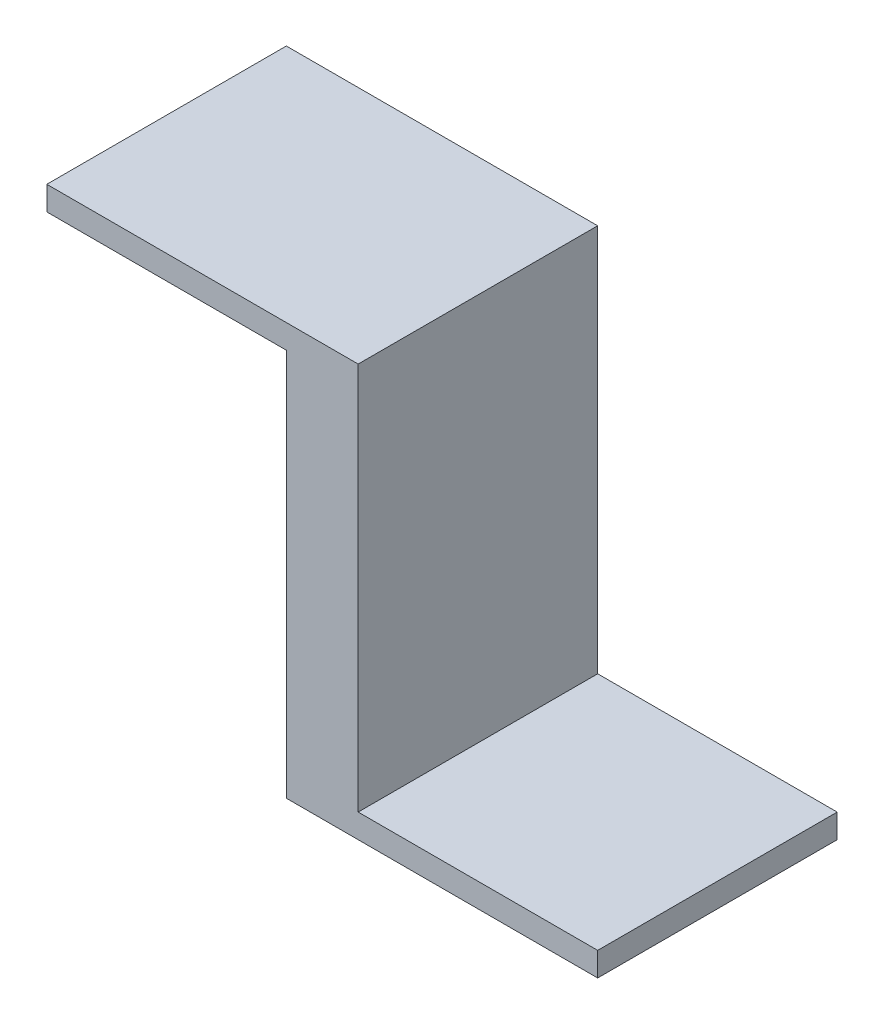
SolidWorks part; units mm, degrees
ref_plane "Front Plane" through (0, 0, 0) normal (0, 0, 1) x (1, 0, 0)
ref_plane "Top Plane" through (0, 0, 0) normal (0, 1, 0) x (1, 0, 0)
ref_plane "Right Plane" through (0, 0, 0) normal (1, 0, 0) x (0, 0, -1)
sketch "Sketch1" plane through (0, 0, 0) normal (0, 0, 1) x (1, 0, 0)
  line L0 (0, 0) -> (65, 0)
  line L6 (0, 0) -> (0, 81)
  line L12 (15, 5) -> (15, 86)
  line L15 (0, 81) -> (-50, 81)
  line L16 (-50, 86) -> (-50, 81)
  line L17 (15, 5) -> (65, 5)
  line L20 (65, 5) -> (65, 0)
  line L21 (-50, 86) -> (15, 86)
  dimension "D1" = 81
  dimension "D2" = 15
  dimension "D3" = 50
  dimension "D4" = 50
  dimension "D5" = 5
  dimension "D6" = 5
extrude "Boss-Extrude1" add sketch "Sketch1" along normal blind 50
